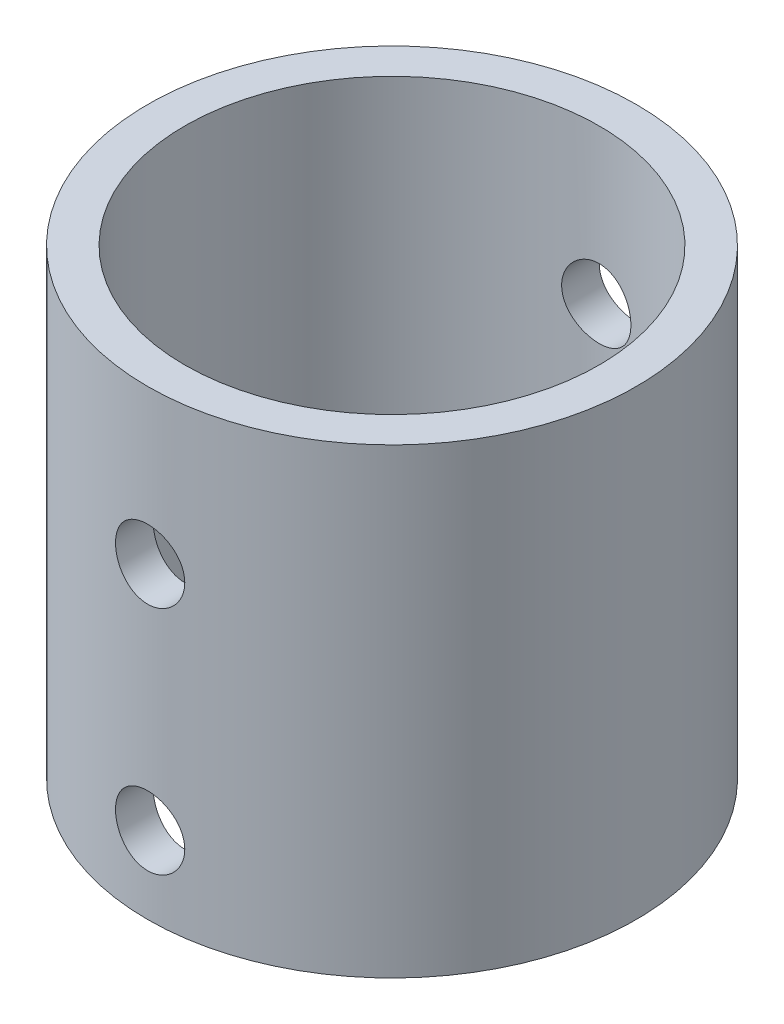
SolidWorks part; units mm, degrees
ref_plane "Front Plane" through (0, 0, 0) normal (0, 0, 1) x (1, 0, 0)
ref_plane "Top Plane" through (0, 0, 0) normal (0, 1, 0) x (1, 0, 0)
ref_plane "Right Plane" through (0, 0, 0) normal (1, 0, 0) x (0, 0, -1)
sketch "Sketch1" plane through (0, 0, 0) normal (0, 1, 0) x (1, 0, 0)
  circle A0 centre (0, 0) radius 13.462
  circle A1 centre (0, 0) radius 15.875
  dimension "D1" = 31.75
  dimension "D2" = 2.413
extrude "Boss-Extrude1" add sketch "Sketch1" against normal blind 30
sketch "Sketch2" plane through (0, 0, 0) normal (0, 0, 1) x (1, 0, 0)
  line L0 (0, 0) -> (0, -30) construction
  line L1 (-15.875, -30) -> (15.875, -30) construction
  circle A0 centre (0, -25) radius 2.25
  circle A1 centre (0, -10) radius 2.25
  dimension "D1" = 4.5
  dimension "D2" = 10
  dimension "D3" = 15
  dimension "D4" = 5
extrude "Cut-Extrude1" cut sketch "Sketch2" against normal blind 30 and the other way blind 30
